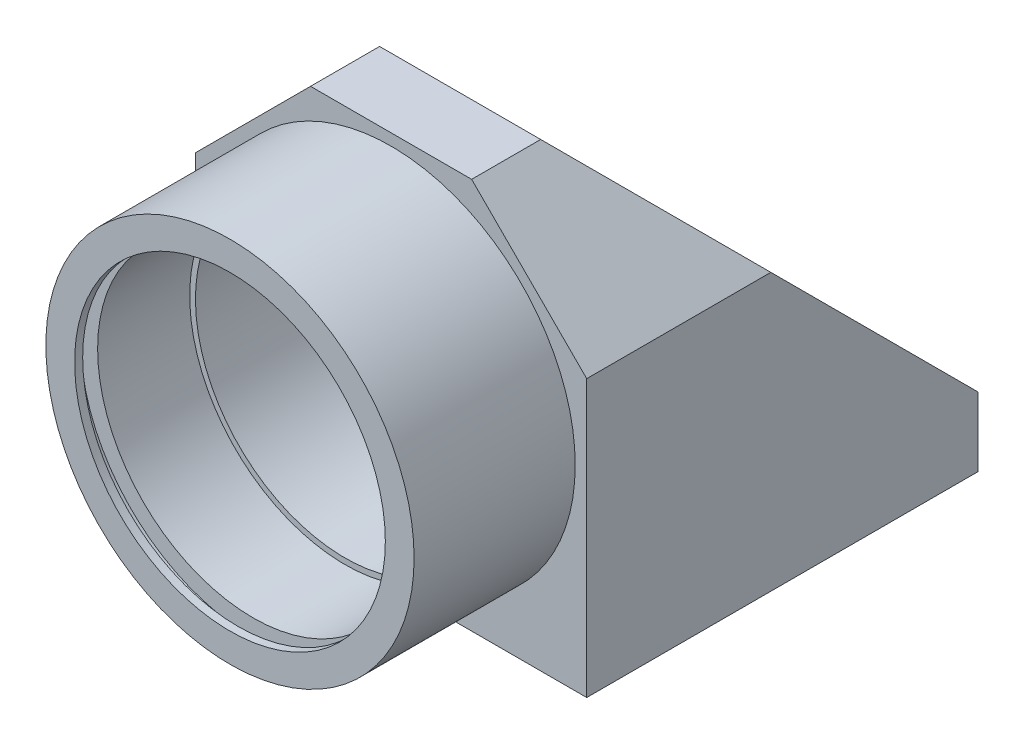
SolidWorks part; units mm, degrees
material "1060 合金"
ref_plane "前视基准面" through (0, 0, 0) normal (0, 0, 1) x (1, 0, 0)
ref_plane "上视基准面" through (0, 0, 0) normal (0, 1, 0) x (1, 0, 0)
ref_plane "右视基准面" through (0, 0, 0) normal (1, 0, 0) x (0, 0, -1)
sketch "草图1" plane through (0, 0, 0) normal (0, 0, 1) x (1, 0, 0)
  line L0 (0, 0) -> (0, 67.9685) construction
  line L1 (0, 0) -> (83.4241, 0) construction
  line L3 (-17, -17) -> (17, -17)
  line L4 (-17, -17) -> (-17, 17)
  line L5 (-17, 17) -> (17, 17)
  line L6 (17, -17) -> (17, 17)
  line L7 (-17, -17) -> (17, 17) construction
  line L8 (-17, 17) -> (17, -17) construction
  circle A0 centre (0, 0) radius 13
  dimension "D1" = 26
  dimension "D2" = 34
  dimension "D3" = 34
extrude "凸台-拉伸1" add sketch "草图1" along normal blind 48
sketch "草图2" plane through (0, 0, 48) normal (0, 0, 1) x (1, 0, 0)
  circle A0 centre (0, 0) radius 13.5
  dimension "D1" = 27
extrude "切除-拉伸1" cut sketch "草图2" against normal blind 10
sketch "草图3" plane through (0, -17, 0) normal (0, -1, 0) x (1, 0, 0)
  line L0 (0, 0) -> (0, 57.5158) construction
  line L1 (-17, 48) -> (17, 48) construction
  circle A0 centre (0, 17) radius 13
  dimension "D1" = 26
  dimension "D2" = 31
extrude "切除-拉伸2" cut sketch "草图3" against normal blind 10
chamfer "倒角1" distance 10 angle 45 2 edges at (17, 17, 24) (-17, 17, 24)
chamfer "倒角2" distance 28 angle 45 1 edges at (0, 17, 0)
sketch "草图5" plane through (0, 0, 48) normal (0, 0, 1) x (1, 0, 0)
  line L0 (-7, 17) -> (-17, 7)
  line L1 (-17, 7) -> (-17, -17)
  line L2 (-17, -17) -> (17, -17)
  line L3 (17, -17) -> (17, 7)
  line L4 (17, 7) -> (7, 17)
  line L5 (7, 17) -> (-7, 17)
  circle A0 centre (0, 0) radius 16
  circle A1 centre (0, 0) radius 13.5 construction
  dimension "D1" = 2.5
extrude "切除-拉伸4" cut sketch "草图5" against normal blind 14
hole_wizard "M4 螺纹孔1" positions "草图7" profile "草图6" tap size "M4" standard "GB"
sketch "草图7" plane through (0, -17, 0) normal (0, -1, 0) x (1, 0, 0)
  line L0 (0, 17) -> (21.032, 38.032) construction
  line L2 (17, 34) -> (17, 0) construction
  line L3 (0, 17) -> (26.7129, 17) construction
  point P0 (13, 30)
  point P14 (13, 4)
  point P15 (-13, 4)
  point P16 (-13, 30)
  dimension "D1" = 4
  dimension "D3" = 45
  dimension "D2" = 4
sketch "草图6" plane through (13, -17, 30) normal (1, 0, 0) x (0, 0, -1)
  line L0 (0, 0) -> (0, 8.9914)
  line L1 (0, 8.9914) -> (1.65, 8)
  line L2 (1.65, 8) -> (1.65, 0)
  line L5 (1.65, 0) -> (0, 0)
  line L10 (0, 8.9914) -> (-1.65, 8) construction
  line L11 (0, -6.35) -> (0, 107.95) construction
  dimension "螺纹孔钻头直径" = 3.3
  dimension "螺纹孔钻头深度" = 8
  dimension "导头角度" = 118
cosmetic thread "孔螺蚊线1" parameters "D1"=8, "D2"=4
cosmetic thread "孔螺蚊线2" parameters "D1"=8, "D2"=4
cosmetic thread "孔螺蚊线3" parameters "D1"=8, "D2"=4
cosmetic thread "孔螺蚊线4" parameters "D1"=8, "D2"=4
sketch "草图8" plane through (0, 0, 0) normal (1, 0, 0) x (0, 0, -1)
  line L0 (0, 0) -> (-57.5114, 0) construction
  line L1 (-38, 13.5) -> (-48, 13.5) construction
  line L2 (-46, 13.5) -> (-47.3, 13.5)
  line L3 (-46, 13.5) -> (-46, 15)
  line L4 (-46, 15) -> (-47.3, 15)
  line L5 (-47.3, 13.5) -> (-47.3, 15)
  line L6 (-48, 16) -> (-48, -16) construction
  dimension "D1" = 1.3
  dimension "D2" = 2
  dimension "D3" = 15
revolve "切除-旋转1" cut sketch "草图8" angle 360 about L0
sketch "草图9" plane through (0, 0, 34) normal (0, 0, 1) x (1, 0, 0)
  line L0 (0, 0) -> (30.6315, 0) construction
  line L1 (17, -17) -> (17, 7) construction
  line L2 (25, 7) -> (17, 7)
  line L3 (25, 7) -> (25, -7)
  line L4 (25, -7) -> (17, -7)
  line L5 (17, 7) -> (17, -7)
  line L6 (25, 7) -> (17, -7) construction
  line L7 (25, -7) -> (17, 7) construction
  line L8 (21, 9.6972) -> (21, -9.1795) construction
  point P3 (21, 0)
  dimension "D1" = 14
  dimension "D2" = 8
extrude "凸台-拉伸2" [suppressed] add sketch "草图9" against normal blind 7
